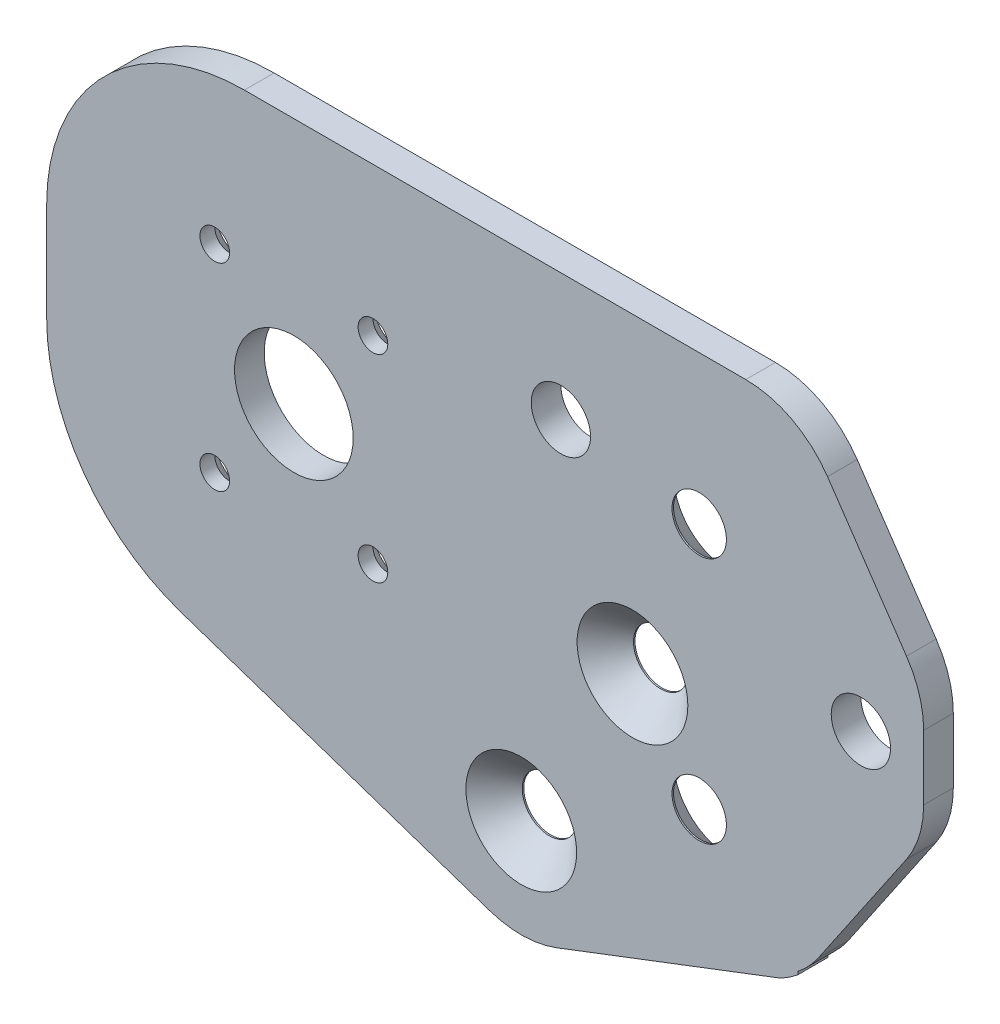
SolidWorks part; units mm, degrees
material "Gerais  - 6061-T6"
ref_plane "Plano frontal" through (0, 0, 0) normal (0, 0, 1) x (1, 0, 0)
ref_plane "Plano superior" through (0, 0, 0) normal (0, 1, 0) x (1, 0, 0)
ref_plane "Plano direito" through (0, 0, 0) normal (1, 0, 0) x (0, 0, -1)
sketch "Esboço1" plane through (0, 0, 0) normal (0, 0, 1) x (1, 0, 0)
  line L0 (56, 50) -> (56, 0) construction
  line L1 (0, 0) -> (76, 0)
  line L2 (0, 0) -> (0, 50)
  line L3 (0, 50) -> (76, 50)
  line L4 (76, 0) -> (76, 50)
  line L5 (66, 50) -> (66, 18.5) construction
  line L6 (65.25, 50) -> (65.25, 18.5) construction
  line L7 (59.25, 12.5) -> (25, 12.5) construction
  circle A0 centre (25, 25) radius 16 construction
  circle A1 centre (59.25, 18.5) radius 9.75 construction
  circle A2 centre (59.25, 18.5) radius 6 construction
  circle A3 centre (25, 25) radius 12.5 construction
  circle A4 centre (59.25, 18.5) radius 2.5
  circle A5 centre (25, 25) radius 6
  circle A6 centre (17, 38.8564) radius 1.5 construction
  circle A7 centre (33, 38.8564) radius 1.5 construction
  circle A8 centre (41, 25) radius 1.5 construction
  circle A9 centre (33, 11.1436) radius 1.5 construction
  circle A10 centre (17, 11.1436) radius 1.5 construction
  circle A11 centre (9, 25) radius 1.5 construction
  point P7 (41, 25)
  point P36 (25, 25)
  dimension "D1" = 32
  dimension "D5" = 12
  dimension "D6" = 19.5
  dimension "D9" = 25
  dimension "D10" = 5
  dimension "D13" = 12
  dimension "D14" = 3
  dimension "D2" = 25
  dimension "D3" = 35
  dimension "D4" = 20
  dimension "D7" = 0.75
  dimension "D8" = 10
  dimension "D11" = 25
  dimension "D12" = 50
  dimension "D15" = 6
extrude "Ressalto-extrusão1" add sketch "Esboço1" along normal blind 3
sketch "Esboço2" plane through (0, 0, 3) normal (0, 0, 1) x (1, 0, 0)
  line L0 (66, 50) -> (66, 0) construction
  line L1 (76, 50) -> (0, 50) construction
  line L2 (0, 0) -> (76, 0) construction
  line L3 (76, 0) -> (76, 50) construction
  circle A0 centre (66, 35) radius 2.5
  circle A1 centre (66, 10) radius 2.5
  dimension "D2" = 5
  dimension "D3" = 5
  dimension "D1" = 10
  dimension "D4" = 10
  dimension "D5" = 15
extrude "Corte-extrusão1" cut sketch "Esboço2" against normal blind 3
fillet "Filete1" radius 20 2 edges at (0, 0, 1.5) (0, 50, 1.5)
sketch "Esboço3" plane through (0, 0, 3) normal (0, 0, 1) x (1, 0, 0)
  line L1 (17, 15) -> (33, 15) construction
  line L2 (17, 15) -> (17, 35) construction
  line L3 (17, 35) -> (33, 35) construction
  line L4 (33, 15) -> (33, 35) construction
  line L5 (17, 15) -> (33, 35) construction
  line L6 (17, 35) -> (33, 15) construction
  circle A0 centre (33, 35) radius 1.5
  circle A1 centre (33, 15) radius 1.5
  circle A2 centre (17, 15) radius 1.5
  circle A3 centre (17, 35) radius 1.5
  point P0 (25, 25)
  dimension "D3" = 3
  dimension "D1" = 20
  dimension "D2" = 16
extrude "Corte-extrusão2" cut sketch "Esboço3" against normal through all
sketch "Esboço4" plane through (0, 0, 3) normal (0, 0, 1) x (1, 0, 0)
  line L0 (76, 50) -> (20, 50) construction
  line L1 (55.3323, 43.65) -> (51.6662, 50) construction
  line L2 (51.6662, 50) -> (44.3338, 50) construction
  line L3 (44.3338, 50) -> (40.6677, 43.65) construction
  line L4 (40.6677, 43.65) -> (44.3338, 37.3) construction
  line L5 (44.3338, 37.3) -> (51.6662, 37.3) construction
  line L6 (51.6662, 37.3) -> (55.3323, 43.65) construction
  line L7 (76, 0) -> (76, 50) construction
  line L8 (76, 0) -> (76, 50) construction
  line L9 (51.4498, -6.4701) -> (55.3282, -0.2474) construction
  line L10 (55.3282, -0.2474) -> (51.8783, 6.2227) construction
  line L11 (51.8783, 6.2227) -> (44.5502, 6.4701) construction
  line L12 (44.5502, 6.4701) -> (40.6718, 0.2474) construction
  line L13 (40.6718, 0.2474) -> (44.1217, -6.2227) construction
  line L14 (44.1217, -6.2227) -> (51.4498, -6.4701) construction
  line L15 (25, 12.5) -> (61.6574, 12.5) construction
  line L16 (20, 0) -> (76, 0) construction
  line L17 (48, 43.65) -> (48, 0) construction
  circle A0 centre (48, 43.65) radius 3 construction
  circle A1 centre (48, 43.65) radius 6.35 construction
  circle A2 centre (48, 0) radius 2.5
  circle A3 centre (48, 0) radius 6.35 construction
  arc A4 (17.8926, 14.7172) -> (30.3514, 13.7035) centre (25, 25) ccw construction
  arc A5 (17.8926, 14.7172) -> (30.3514, 13.7035) centre (25, 25) ccw construction
  circle A6 centre (52.0071, 37.1424) radius 3
  circle A7 centre (25, 25) radius 29.6112 construction
  circle A8 centre (59.25, 18.5) radius 2.5 construction
  point P34 (0, 0)
  dimension "D1" = 12.7
  dimension "D3" = 6
  dimension "D4" = 5
  dimension "D6" = 20
  dimension "D2" = 28
  dimension "D5" = 28
extrude "Corte-extrusão3" cut sketch "Esboço4" against normal through all
sketch "Esboço5" plane through (0, 0, 0) normal (0, 0, -1) x (-1, 0, 0)
  line L0 (-76, 0) -> (-51.5714, -9.3405)
  line L1 (-44.8034, -9.4753) -> (-13.6067, 1.0494)
  line L2 (-20, 0) -> (-45.5, 0) construction
  line L3 (-50.5, 0) -> (-76, 0) construction
  line L4 (-20, 0) -> (-45.5, 0)
  line L5 (-50.5, 0) -> (-76, 0)
  circle A0 centre (-48, 0) radius 2.5
  arc A1 (-51.5714, -9.3405) -> (-44.8034, -9.4753) centre (-48, 0) ccw
  arc A2 (-20, 0) -> (0, 20) centre (-20, 20) ccw construction
  line M5 (-45.5, 0) -> (-20, 0)
  arc M6 (-20, 0) -> (0, 20) centre (-20, 20) ccw
  line M11 (-76, 0) -> (-50.5, 0)
  dimension "D1" = 20
extrude "Ressalto-extrusão2" add sketch "Esboço5" against normal through all contours L0 A1 L1 A0 M6 M5 M11 region at (46.8798, -3.5834, 0)
sketch "Esboço6" plane through (0, 0, 0) normal (0, 0, -1) x (-1, 0, 0)
  line L7 (-86.9656, 16.103) -> (-78.0603, 3.0256)
  line L8 (-72.4733, -0.9805) -> (-50.0089, -7.2259)
  line L9 (-46.1556, -7.2697) -> (-15.0816, 0.6142)
  line L10 (0, 20) -> (0, 30)
  line L11 (-20, 50) -> (-70.7112, 50)
  line L12 (-78.9768, 45.6286) -> (-86.9656, 33.897)
  line L13 (-88.7, 28.2685) -> (-88.7, 21.7315)
  line L14 (-86.9656, 16.103) -> (-78.0603, 3.0256)
  line L15 (-72.4733, -0.9805) -> (-50.0089, -7.2259)
  line L16 (-46.1556, -7.2697) -> (-15.0816, 0.6142)
  line L17 (0, 20) -> (0, 30)
  line L18 (-20, 50) -> (-70.7112, 50)
  line L19 (-78.9768, 45.6286) -> (-86.9656, 33.897)
  line L20 (-88.7, 28.2685) -> (-88.7, 21.7315)
  circle A0 centre (-82.35, 25) radius 3 construction
  circle A1 centre (-82.35, 25) radius 3
  arc A7 (-78.0603, 3.0256) -> (-72.4733, -0.9805) centre (-69.7947, 8.6541) ccw
  arc A8 (-50.0089, -7.2259) -> (-46.1556, -7.2697) centre (-48, 0) ccw
  arc A9 (-15.0816, 0.6142) -> (0, 20) centre (-20, 20) ccw
  arc A10 (0, 30) -> (-20, 50) centre (-20, 30) ccw
  arc A11 (-70.7112, 50) -> (-78.9768, 45.6286) centre (-70.7112, 40) ccw
  arc A12 (-86.9656, 33.897) -> (-88.7, 28.2685) centre (-78.7, 28.2685) ccw
  arc A13 (-88.7, 21.7315) -> (-86.9656, 16.103) centre (-78.7, 21.7315) ccw
  arc A15 (-50.0089, -7.2259) -> (-46.1556, -7.2697) centre (-48, 0) ccw
  arc A16 (-15.0816, 0.6142) -> (0, 20) centre (-20, 20) ccw
  arc A17 (0, 30) -> (-20, 50) centre (-20, 30) ccw
  arc A18 (-70.7112, 50) -> (-78.9768, 45.6286) centre (-70.7112, 40) ccw
  arc A19 (-86.9656, 33.897) -> (-88.7, 28.2685) centre (-78.7, 28.2685) ccw
  arc A20 (-88.7, 21.7315) -> (-86.9656, 16.103) centre (-78.7, 21.7315) ccw
  arc A54 (-78.0603, 3.0256) -> (-72.4733, -0.9805) centre (-69.7947, 8.6541) ccw
  line M16 (-76, 50) -> (-76, 0)
  dimension "D1" = 0
extrude "Ressalto-extrusão3" add sketch "Esboço6" against normal through all contours L20 A20 L14 A54 A18 L19 A19 A1 M16 region at (87.7851, 18.9319, 0)
sketch "Esboço7" plane through (0, 0, 0) normal (0, 0, -1) x (-1, 0, 0)
  line L0 (-76, 0) -> (-51.5714, -9.3405) construction
  line L9 (-76, 0.8122) -> (-76, 0)
  line L10 (-76, 0) -> (-51.5714, -9.3405)
  line L11 (-44.8034, -9.4753) -> (-13.6067, 1.0494)
  line L12 (0, 20) -> (0, 30)
  line L13 (-20, 50) -> (-76, 50)
  line L14 (-20, 50) -> (-76, 50)
  line L15 (-78.9768, 45.6286) -> (-86.9656, 33.897)
  line L16 (-88.7, 28.2685) -> (-88.7, 21.7315)
  line L17 (-86.9656, 16.103) -> (-78.0603, 3.0256)
  line L18 (-76, 0.8122) -> (-76, 0)
  line L19 (-76, 0) -> (-51.5714, -9.3405)
  line L20 (-44.8034, -9.4753) -> (-13.6067, 1.0494)
  line L21 (0, 20) -> (0, 30)
  line L24 (-78.9768, 45.6286) -> (-86.9656, 33.897)
  line L25 (-88.7, 28.2685) -> (-88.7, 21.7315)
  line L26 (-86.9656, 16.103) -> (-78.0603, 3.0256)
  line L28 (-76, 50) -> (-76, 48.487)
  line L29 (-76, 50) -> (-76, 48.487)
  arc A0 (-78.9768, 45.6286) -> (-70.7112, 50) centre (-70.7112, 40) cw
  arc A1 (-78.0603, 3.0256) -> (-72.5961, -1.3015) centre (-70.1034, 7.4599) ccw
  arc A7 (-51.5714, -9.3405) -> (-44.8034, -9.4753) centre (-48, 0) ccw
  arc A8 (-13.6067, 1.0494) -> (0, 20) centre (-20, 20) ccw
  arc A9 (0, 30) -> (-20, 50) centre (-20, 30) ccw
  arc A10 (-76, 48.487) -> (-78.9768, 45.6286) centre (-70.7112, 40) ccw
  arc A11 (-86.9656, 33.897) -> (-88.7, 28.2685) centre (-78.7, 28.2685) ccw
  arc A12 (-88.7, 21.7315) -> (-86.9656, 16.103) centre (-78.7, 21.7315) ccw
  arc A14 (-51.5714, -9.3405) -> (-44.8034, -9.4753) centre (-48, 0) ccw
  arc A15 (-13.6067, 1.0494) -> (0, 20) centre (-20, 20) ccw
  arc A17 (-76, 48.487) -> (-78.9768, 45.6286) centre (-70.7112, 40) ccw
  arc A18 (-86.9656, 33.897) -> (-88.7, 28.2685) centre (-78.7, 28.2685) ccw
  arc A19 (-88.7, 21.7315) -> (-86.9656, 16.103) centre (-78.7, 21.7315) ccw
  arc A22 (-78.0603, 3.0256) -> (-76, 0.8122) centre (-69.7947, 8.6541) ccw
  arc A23 (-78.0603, 3.0256) -> (-76, 0.8122) centre (-69.7947, 8.6541) ccw
  arc A24 (0, 30) -> (-20, 50) centre (-20, 30) ccw
  point P14 (-69.7947, 8.6541)
  line M18 (-76, 0.8122) -> (-76, 0)
  line M19 (-76, 0) -> (-51.5714, -9.3405)
  line M26 (-76, 50) -> (-76, 48.487)
  dimension "D1" = 0
extrude "Corte-extrusão4" cut sketch "Esboço7" against normal through all contours A1 M18 M19 | A0 L14 M26 region at (75.4496, -0.0541, 0) region at (74.6987, 49.5527, 0)
chamfer "Chanfro1" distance 1.5 angle 45 4 edges at (18.5, 35, 0) (18.5, 15, 0) (34.5, 15, 0) (34.5, 35, 0)
hole_wizard "Escareado para SFHCS M51" positions "Esboço16" profile "Esboço17" countersink size "M5" standard "Ansi Metric" end condition through all
sketch "Esboço16" plane through (0, 0, 3) normal (0, 0, 1) x (1, 0, 0)
  point P0 (48, 0)
sketch "Esboço17" plane through (48, 0, 3) normal (1, 0, 0) x (0, -1, 0)
  line L0 (0, 0) -> (0, 3)
  line L1 (0, 3) -> (2.75, 3)
  line L2 (2.75, 3) -> (2.75, 2.85)
  line L3 (2.75, 2.85) -> (5.6, 0)
  line L5 (5.6, 0) -> (0, 0)
  line L6 (-2.75, 2.85) -> (-5.6, 0) construction
  line L11 (0, -6.35) -> (0, 107.95) construction
  dimension "Thru Hole Dia." = 5.5
  dimension "Thru Hole Depth" = 3
  dimension "Near C'Sink Dia." = 11.2
  dimension "Near C'Sink Angle" = 90
hole_wizard "Escareado para SFHCS M52" positions "Esboço18" profile "Esboço19" countersink size "M5" standard "Ansi Metric" end condition through all
sketch "Esboço18" plane through (0, 0, 3) normal (0, 0, 1) x (1, 0, 0)
  point P0 (59.25, 18.5)
sketch "Esboço19" plane through (59.25, 18.5, 3) normal (1, 0, 0) x (0, -1, 0)
  line L0 (0, 0) -> (0, 3)
  line L1 (0, 3) -> (2.75, 3)
  line L2 (2.75, 3) -> (2.75, 2.85)
  line L3 (2.75, 2.85) -> (5.6, 0)
  line L5 (5.6, 0) -> (0, 0)
  line L6 (-2.75, 2.85) -> (-5.6, 0) construction
  line L11 (0, -6.35) -> (0, 107.95) construction
  dimension "Thru Hole Dia." = 5.5
  dimension "Thru Hole Depth" = 3
  dimension "Near C'Sink Dia." = 11.2
  dimension "Near C'Sink Angle" = 90
hole_wizard "Escareado para SFHCS M54" positions "Esboço22" profile "Esboço23" countersink size "M5" standard "Ansi Metric" end condition through all
sketch "Esboço22" plane through (0, 0, 0) normal (0, 0, -1) x (-1, 0, 0)
  point P0 (-66, 35)
  point P3 (-66, 10)
sketch "Esboço23" plane through (66, 35, 0) normal (1, 0, 0) x (0, 1, 0)
  line L0 (0, 0) -> (0, 3)
  line L1 (0, 3) -> (2.75, 3)
  line L2 (2.75, 3) -> (2.75, 2.85)
  line L3 (2.75, 2.85) -> (5.6, 0)
  line L5 (5.6, 0) -> (0, 0)
  line L6 (-2.75, 2.85) -> (-5.6, 0) construction
  line L11 (0, -6.35) -> (0, 107.95) construction
  dimension "Thru Hole Dia." = 5.5
  dimension "Thru Hole Depth" = 3
  dimension "Near C'Sink Dia." = 11.2
  dimension "Near C'Sink Angle" = 90
